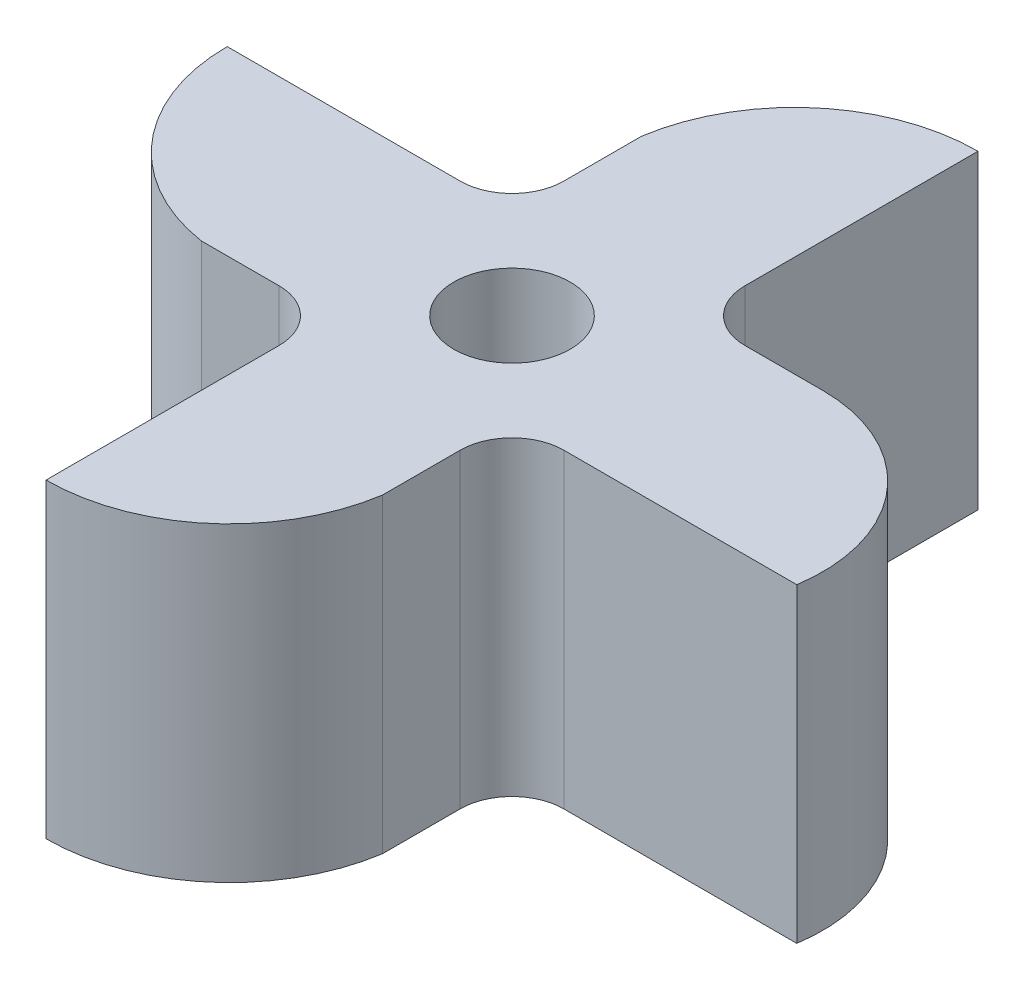
SolidWorks part; units mm, degrees
ref_plane "Front Plane" through (0, 0, 0) normal (0, 0, 1) x (1, 0, 0)
ref_plane "Top Plane" through (0, 0, 0) normal (0, 1, 0) x (1, 0, 0)
ref_plane "Right Plane" through (0, 0, 0) normal (1, 0, 0) x (0, 0, -1)
sketch "Sketch1" plane through (0, 0, 0) normal (0, 1, 0) x (1, 0, 0)
  line L0 (0, 0) -> (30.0302, 0) construction
  line L1 (0, 0) -> (-24.5958, 0) construction
  line L2 (3.5, 5.5) -> (3.5, 14.5)
  line L3 (-3.5, 5.5) -> (-3.5, 8.5)
  line L4 (0, 0) -> (0, 20.3555) construction
  line L5 (0, 0) -> (0, -21.9329) construction
  line L6 (-3.5, -5.5) -> (-3.5, -14.5)
  line L7 (3.5, -5.5) -> (3.5, -8.5)
  line L8 (5.5, 3.5) -> (8.5, 3.5)
  line L9 (5.5, -3.5) -> (14.5, -3.5)
  line L10 (-5.5, 3.5) -> (-14.5, 3.5)
  line L11 (-5.5, -3.5) -> (-8.5, -3.5)
  circle A0 centre (0, 0) radius 2.25
  arc A1 (3.5, 14.5) -> (-3.5, 8.5) centre (3.5, 7.4167) ccw
  arc A2 (-3.5, -14.5) -> (3.5, -8.5) centre (-3.5, -7.4167) ccw
  arc A3 (14.5, -3.5) -> (8.5, 3.5) centre (8.5, -2.5714) ccw
  arc A4 (-14.5, 3.5) -> (-8.5, -3.5) centre (-7.4167, 3.5) ccw
  arc A5 (-3.5, -5.5) -> (-5.5, -3.5) centre (-5.5, -5.5) ccw
  arc A6 (5.5, -3.5) -> (3.5, -5.5) centre (5.5, -5.5) ccw
  arc A7 (-3.5, 5.5) -> (-5.5, 3.5) centre (-5.5, 5.5) cw
  arc A8 (3.5, 5.5) -> (5.5, 3.5) centre (5.5, 5.5) ccw
  point P26 (-3.5, -3.5)
  point P29 (3.5, -3.5)
  point P32 (-3.5, 3.5)
  point P35 (3.5, 3.5)
  dimension "D1" = 4.5
  dimension "D16" = 2
  dimension "D17" = 2
  dimension "D18" = 2
  dimension "D19" = 2
  dimension "D2" = 3.5
  dimension "D3" = 3.5
  dimension "D4" = 6
  dimension "D5" = 3.5
  dimension "D6" = 3.5
  dimension "D7" = 6
  dimension "D8" = 6
  dimension "D9" = 11
  dimension "D10" = 3.5
  dimension "D11" = 3.5
  dimension "D12" = 11
  dimension "D13" = 11
  dimension "D14" = 6
  dimension "D15" = 11
extrude "Boss-Extrude1" add sketch "Sketch1" along normal blind 12 contours L6 A2 L7 A6 L9 A3 L8 A8 L2 A1 L3 A7 L10 A4 L11 A5 | A0
